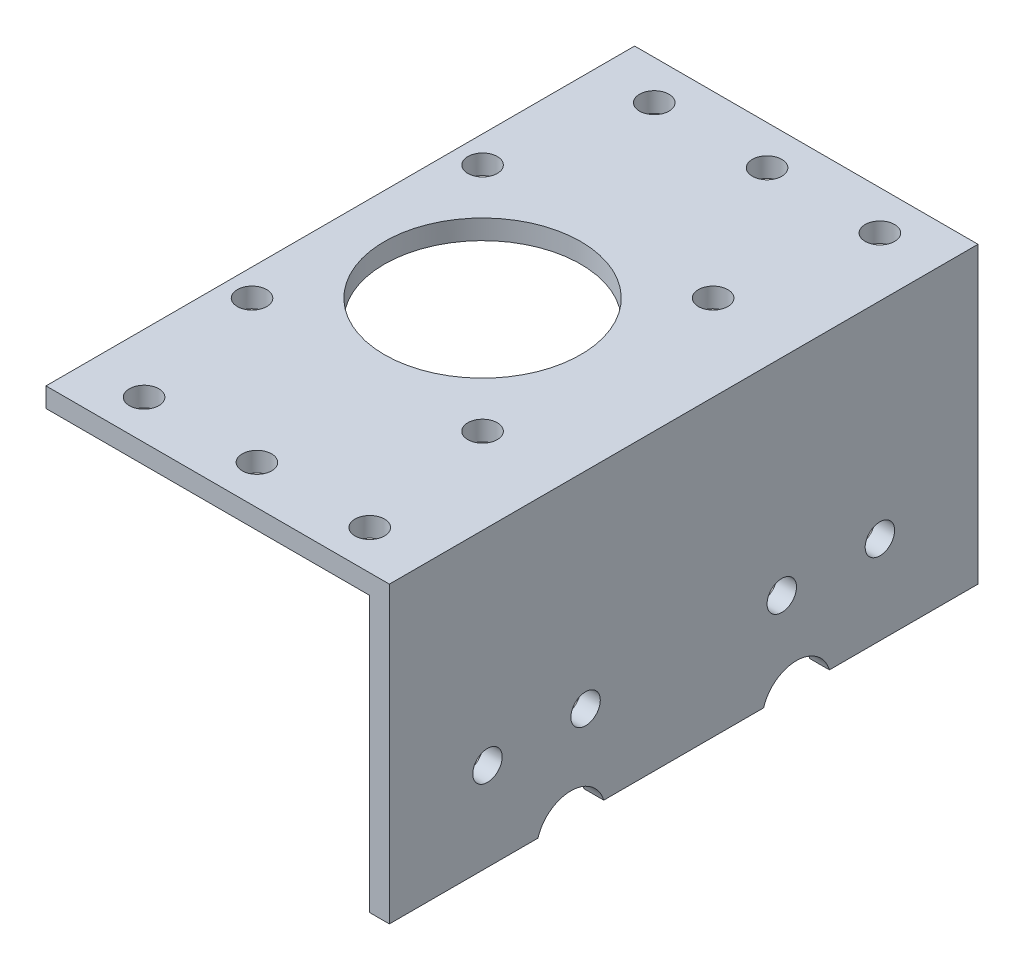
SolidWorks part; units mm, degrees
material "3.3547 (EN-AW 5083)"
ref_plane "Ebene vorne" through (0, 0, 0) normal (0, 0, 1) x (1, 0, 0)
ref_plane "Ebene oben" through (0, 0, 0) normal (0, 1, 0) x (1, 0, 0)
ref_plane "Ebene rechts" through (0, 0, 0) normal (1, 0, 0) x (0, 0, -1)
sketch "Skizze1" plane through (0, 0, 0) normal (0, 0, 1) x (1, 0, 0)
  line L0 (-70, 0) -> (0, 0)
  line L1 (0, 0) -> (0, -60)
  line L2 (0, -60) -> (-4, -60)
  line L3 (-4, -60) -> (-4, -4)
  line L4 (-4, -4) -> (-70, -4)
  line L5 (-70, -4) -> (-70, 0)
  dimension "D1" = 70
  dimension "D2" = 60
  dimension "D3" = 4
extrude "Aufsatz-Linear austragen1" add sketch "Skizze1" along normal mid plane 120
sketch "Skizze2" plane through (0, 0, 0) normal (0, 1, 0) x (1, 0, 0)
  line L0 (0, 0) -> (-96.695, 0) construction
  line L1 (0, -60) -> (0, 60) construction
  line L2 (-41, 0) -> (-41, 31.0432) construction
  circle A0 centre (-41, 0) radius 20
  circle A1 centre (-17.5, 23.5) radius 3
  circle A2 centre (-64.5, 23.5) radius 3
  circle A3 centre (-17.5, -23.5) radius 3
  circle A4 centre (-64.5, -23.5) radius 3
  dimension "D1" = 40
  dimension "D2" = 6
  dimension "D3" = 47
  dimension "D4" = 47
  dimension "D5" = 41
extrude "Schnitt-Linear austragen1" cut sketch "Skizze2" against normal blind 20
sketch "Skizze3" plane through (0, 0, 0) normal (1, 0, 0) x (0, 0, -1)
  line L0 (0, 0) -> (0, -60) construction
  line L1 (-60, -60) -> (60, -60) construction
  line L2 (40, -42) -> (20, -42) construction
  line L3 (-60, 0) -> (60, 0) construction
  circle A0 centre (40, -42) radius 3
  circle A1 centre (-40, -42) radius 3
  circle A4 centre (20, -42) radius 3
  circle A5 centre (-20, -42) radius 3
  dimension "D1" = 42
  dimension "D2" = 40
  dimension "D3" = 6
  dimension "D4" = 80
extrude "Schnitt-Linear austragen2" cut sketch "Skizze3" against normal blind 20
sketch "Skizze4" plane through (0, 0, 0) normal (1, 0, 0) x (0, 0, -1)
  line L0 (0, 0) -> (0, -75.2195) construction
  line L2 (-60, -60) -> (60, -60) construction
  circle A0 centre (23, -62) radius 7
  circle A1 centre (-23, -62) radius 7
  dimension "D1" = 46
  dimension "D2" = 14
  dimension "D3" = 2
extrude "Schnitt-Linear austragen3" cut sketch "Skizze4" against normal blind 10
sketch "Skizze5" plane through (0, 0, 0) normal (0, 1, 0) x (1, 0, 0)
  line L0 (0, 0) -> (-90.5453, 0) construction
  line L1 (-58, -52) -> (-12, -52) construction
  line L2 (0, -60) -> (-70, -60) construction
  line L3 (0, -60) -> (0, 60) construction
  line L4 (-70, -60) -> (-70, 60) construction
  circle A0 centre (-58, -52) radius 3
  circle A1 centre (-35, -52) radius 3
  circle A2 centre (-12, -52) radius 3
  circle A3 centre (-58, 52) radius 3
  circle A4 centre (-35, 52) radius 3
  circle A5 centre (-12, 52) radius 3
  dimension "D2" = 6
  dimension "D3" = 12
  dimension "D4" = 12
  dimension "D1" = 8
extrude "Schnitt-Linear austragen4" cut sketch "Skizze5" against normal blind 10
sketch "Skizze6" plane through (0, 0, 0) normal (0, 1, 0) x (1, 0, 0)
  line L0 (-41, 0) -> (8.8123, 0) construction
  circle A0 centre (-24, 0) radius 3
  circle A1 centre (-41, 0) radius 20 construction
  dimension "D1" = 6
extrude "Aufsatz-Linear austragen2" [suppressed] add sketch "Skizze6" along normal blind 1 separate body
ref_axis "Achse1" [suppressed] through (-41, -4, 0) along (0, 1, 0)
pattern_circular "Kreismuster5" [suppressed] count 16 over 360 about axis through (-41, -4, 0) along (0, 1, 0) of bodies 106
